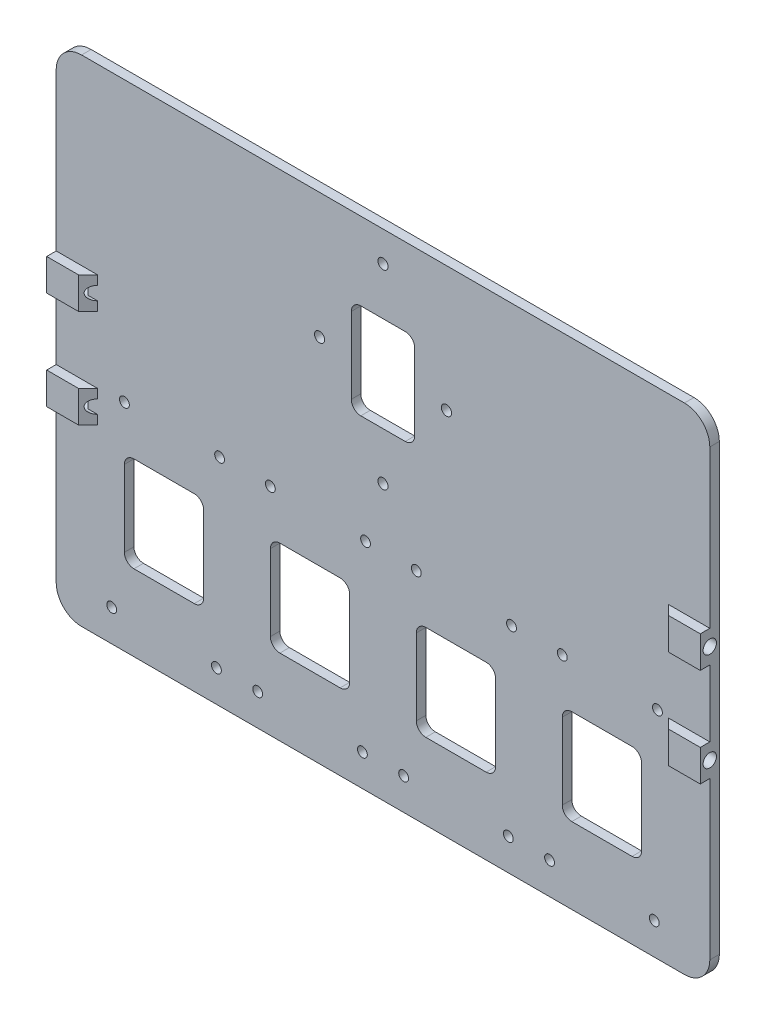
SolidWorks part; units mm, degrees
ref_plane "Front Plane" through (0, 0, 0) normal (1, 0, 0) x (0, 1, 0)
ref_plane "Top Plane" through (0, 0, 0) normal (0, 0, 1) x (0, 1, 0)
ref_plane "Right Plane" through (0, 0, 0) normal (0, 1, 0) x (-1, 0, 0)
sketch "Sketch1" plane through (0, 0, 0) normal (0, 0, 1) x (0, 1, 0)
  line L6 (0, 0) -> (31.4193, 0) construction
  line L7 (-70, -103) -> (70, -103)
  line L8 (-78, -95) -> (-78, 95)
  line L9 (-70, 103) -> (70, 103)
  line L10 (78, -95) -> (78, 95)
  line L11 (-78, -103) -> (78, 103) construction
  line L12 (-78, 103) -> (78, -103) construction
  line L13 (-68, -85.5) -> (-68, -52.5) construction
  line L15 (-10, -86.5) -> (-10, -56.5) construction
  line L23 (38.504, 27.5) -> (38.504, -27.5) construction
  line L25 (-78, 0) -> (-68, 0) construction
  line L30 (68, 0) -> (78, 0) construction
  line L34 (-73, -47.5) -> (-6, -47.5) construction
  line L35 (-73, -47.5) -> (-73, -90.5) construction
  line L40 (-73, -90.5) -> (-6, -90.5) construction
  line L41 (-6, -47.5) -> (-6, -90.5) construction
  line L42 (8.504, 20) -> (68.504, 20) construction
  line L43 (8.504, 20) -> (8.504, -20) construction
  line L44 (8.504, -20) -> (68.504, -20) construction
  line L45 (68.504, 20) -> (68.504, -20) construction
  line L46 (1.004, 27.5) -> (76.004, 27.5) construction
  line L47 (1.004, 27.5) -> (1.004, -27.5) construction
  line L48 (1.004, -27.5) -> (76.004, -27.5) construction
  line L49 (76.004, 27.5) -> (76.004, -27.5) construction
  arc A4 (70, -103) -> (78, -95) centre (70, -95) ccw
  arc A5 (-70, -103) -> (-78, -95) centre (-70, -95) cw
  arc A6 (-78, 95) -> (-70, 103) centre (-70, 95) cw
  arc A7 (70, 103) -> (78, 95) centre (70, 95) cw
  circle A8 centre (-68, -52.5) radius 1.55
  circle A9 centre (-68, -85.5) radius 1.55
  circle A10 centre (-10, -86.5) radius 1.55
  circle A11 centre (-10, -56.5) radius 1.55
  circle A24 centre (-68, -6.5) radius 1.55
  circle A25 centre (-68, -39.5) radius 1.55
  circle A26 centre (-10, -40.5) radius 1.55
  circle A27 centre (-10, -10.5) radius 1.55
  circle A28 centre (-68, 39.5) radius 1.55
  circle A29 centre (-68, 6.5) radius 1.55
  circle A30 centre (-10, 5.5) radius 1.55
  circle A31 centre (-10, 35.5) radius 1.55
  circle A32 centre (-68, 85.5) radius 1.55
  circle A33 centre (-68, 52.5) radius 1.55
  circle A34 centre (-10, 51.5) radius 1.55
  circle A35 centre (-10, 81.5) radius 1.55
  circle A40 centre (8.504, 0) radius 1.6
  circle A41 centre (38.504, 20) radius 1.6
  circle A42 centre (68.504, 0) radius 1.6
  circle A43 centre (38.504, -20) radius 1.6
  point P0 (0, 0)
  point P5 (0, 0)
  dimension "D6" = 8
  dimension "D8" = 3.1
  dimension "D19" = 3.2
  dimension "D1" = 156
  dimension "D3" = 206
  dimension "D7" = 33
  dimension "D10" = 30
  dimension "D5" = 10
  dimension "D4" = 43
  dimension "D11" = 67
  dimension "D12" = 5
  dimension "D13" = 5
  dimension "D9" = 4
  dimension "D15" = 4
  dimension "D16" = 13
  dimension "D17" = 40
  dimension "D18" = 60
  dimension "D21" = 55
  dimension "D22" = 75
  dimension "D20" = 1.996
  dimension "D14" = 4
extrude "Boss-Extrude1" add sketch "Sketch1" along normal blind 3
sketch "Sketch4" plane through (0, 0, 3) normal (0, 0, 1) x (1, 0, 0)
  line L0 (-69, -10) -> (-69, -68) construction
  line L1 (-78.5, -24) -> (-59.5, -24)
  line L2 (-81.5, -27) -> (-81.5, -51)
  line L3 (-78.5, -54) -> (-59.5, -54)
  line L4 (-56.5, -27) -> (-56.5, -51)
  line L5 (-81.5, -10) -> (-51.5, -10) construction
  line L6 (-85.5, -68) -> (-52.5, -68) construction
  line L7 (-81.5, -39) -> (-69, -39) construction
  line L8 (-35.5, -27) -> (-35.5, -51)
  line L9 (-32.5, -24) -> (-13.5, -24)
  line L10 (-32.5, -54) -> (-13.5, -54)
  line L11 (-10.5, -27) -> (-10.5, -51)
  line L12 (10.5, -27) -> (10.5, -51)
  line L13 (13.5, -24) -> (32.5, -24)
  line L14 (13.5, -54) -> (32.5, -54)
  line L15 (35.5, -27) -> (35.5, -51)
  line L16 (56.5, -27) -> (56.5, -51)
  line L17 (59.5, -24) -> (78.5, -24)
  line L18 (59.5, -54) -> (78.5, -54)
  line L19 (81.5, -27) -> (81.5, -51)
  line L20 (69, -8.2965) -> (69, -68) construction
  line L21 (52.5, -68) -> (85.5, -68) construction
  line L22 (-20, 38.504) -> (20, 38.504) construction
  line L23 (-7, 53.504) -> (7, 53.504)
  line L24 (-10, 50.504) -> (-10, 26.504)
  line L25 (-7, 23.504) -> (7, 23.504)
  line L26 (10, 50.504) -> (10, 26.504)
  line L27 (0, 68.504) -> (0, 8.504) construction
  arc A0 (78.5, -54) -> (81.5, -51) centre (78.5, -51) ccw
  arc A1 (78.5, -24) -> (81.5, -27) centre (78.5, -27) cw
  arc A2 (56.5, -27) -> (59.5, -24) centre (59.5, -27) cw
  arc A3 (56.5, -51) -> (59.5, -54) centre (59.5, -51) ccw
  arc A4 (32.5, -24) -> (35.5, -27) centre (32.5, -27) cw
  arc A5 (32.5, -54) -> (35.5, -51) centre (32.5, -51) ccw
  arc A6 (10.5, -51) -> (13.5, -54) centre (13.5, -51) ccw
  arc A7 (10.5, -27) -> (13.5, -24) centre (13.5, -27) cw
  arc A8 (-13.5, -54) -> (-10.5, -51) centre (-13.5, -51) ccw
  arc A9 (-13.5, -24) -> (-10.5, -27) centre (-13.5, -27) cw
  arc A10 (-35.5, -27) -> (-32.5, -24) centre (-32.5, -27) cw
  arc A11 (-35.5, -51) -> (-32.5, -54) centre (-32.5, -51) ccw
  arc A12 (-59.5, -54) -> (-56.5, -51) centre (-59.5, -51) ccw
  arc A13 (-81.5, -51) -> (-78.5, -54) centre (-78.5, -51) ccw
  arc A14 (-59.5, -24) -> (-56.5, -27) centre (-59.5, -27) cw
  arc A15 (-78.5, -24) -> (-81.5, -27) centre (-78.5, -27) ccw
  arc A16 (-10, 26.504) -> (-7, 23.504) centre (-7, 26.504) ccw
  arc A17 (7, 23.504) -> (10, 26.504) centre (7, 26.504) ccw
  arc A18 (7, 53.504) -> (10, 50.504) centre (7, 50.504) cw
  arc A19 (-7, 53.504) -> (-10, 50.504) centre (-7, 50.504) ccw
  point P5 (-58.5, -8.5)
  point P11 (-58.5, -8.5)
  point P67 (-56.5, -54)
  point P72 (-56.5, -24)
  point P75 (-81.5, -24)
  point P98 (10, 23.504)
  point P101 (10, 53.504)
  point P104 (-10, 53.504)
  dimension "D4" = 3
  dimension "D7" = 3
  dimension "D1" = 25
  dimension "D2" = 30
  dimension "D3" = 4
  dimension "D5" = 20
  dimension "D6" = 30
extrude "Cut-Extrude3" cut sketch "Sketch4" against normal up to next
sketch "Sketch3" plane through (103, 0, 0) normal (1, 0, 0) x (0, 1, 0)
  line L0 (0, 3) -> (0, 0) construction
  line L1 (-70, 3) -> (70, 3) construction
  line L2 (-70, 0) -> (70, 0) construction
  line L3 (-20.5, 3) -> (-10.5, 3) construction
  line L7 (-20.5, 6) -> (-10.5, 6)
  line L8 (-20.5, 6) -> (-20.5, 0)
  line L9 (-20.5, 0) -> (-10.5, 0)
  line L10 (-10.5, 6) -> (-10.5, 0)
  line L11 (10.5, 6) -> (20.5, 6)
  line L12 (10.5, 6) -> (10.5, 0)
  line L13 (10.5, 0) -> (20.5, 0)
  line L14 (20.5, 6) -> (20.5, 0)
  circle A1 centre (-15.5, 3) radius 2.1
  circle A2 centre (15.5, 3) radius 2.1
  dimension "D2" = 4.2
  dimension "D3" = 31
  dimension "D4" = 10
  dimension "D5" = 6
extrude "Boss-Extrude2" add sketch "Sketch3" against normal blind 10 contours L7 L10 L9 L8 | L11 L14 L13 L12
extrude "Boss-Extrude3" add sketch "Sketch3<4>" along normal blind 10 from surface contours L10 L9 L8 L7 | L12 L13 L14 L11 starting at face at (-103, 0, 1.5)
sketch "Sketch3<4>" plane through (103, 0, 0) normal (1, 0, 0) x (0, 1, 0) same geometry as "Sketch3"
extrude "Cut-Extrude4" cut sketch "Sketch3<6>" against normal blind 10 contours A1 | A2
sketch "Sketch3<6>" plane through (103, 0, 0) normal (1, 0, 0) x (0, 1, 0) same geometry as "Sketch3"
extrude "Cut-Extrude5" cut sketch "Sketch3<7>" along normal blind 10 from surface contours A2 | A1 starting at face at (-103, 0, 3.5)
sketch "Sketch3<7>" plane through (103, 0, 0) normal (1, 0, 0) x (0, 1, 0) same geometry as "Sketch3"
chamfer "Chamfer1" distance 3 angle 45 4 edges at (93, -19.05, 3) (93, 11.95, 3) (-93, -19.05, 3) (-93, 11.95, 3)
equation "\"MotorDriverLength\"= 60mm"
equation "\"MotorLength\"= 60"
equation "\"MotorDriverWidth\"=44"
equation "\"MotorWidth\"= 37"
equation "\"InnerWallThickness\"=3"
equation "\"BatteryWidth\"= 60"
equation "\"OuterWallThickness\" = 6"
equation "\"CompartmentHeight\"=37"
equation "\"CompartmentWidth\"= \"MotorDriverLength\""
equation "\"MotorDiameter\"=37"
equation "\"BatteryHeight\"=24.2019"
equation "\"MotorDriverHeight\"=28"
equation "\"CircuitHeight\"=30"
equation "\"FanThickness\"= 10"
equation "\"FanHeight\"=50"
equation "\"MotorShaftHole\"=12"
equation "\"BearingBore\"=4"
equation "\"MinShinWidth\"= 20"
equation "\"ShinThickness\"=10"
equation "\"PivotDistance\"=30"
equation "\"ThighLength\"= 200"
equation "\"KneeLength\" =20"
equation "\"HipBore\"=27"
equation "\"ThighThickness\"=20"
equation "\"MaxBending\"=135"
equation "\"MaxStretchingAngle\"= 140"
equation "\"ThighJointDistance\"=157.485"
equation "\"ShinLength\"=120"
equation "\"BearingDiameter\"= 10"
equation "\"CircuitLength\"=50"
equation "\"ChessisInnerWidth\"= \"OuterWallThickness\" * 2 + \"MotorDriverLength\" + \"MotorDiameter\" + \"InnerWallThickness\" * 3 + \"CircuitLength\""
equation "\"ChessisHeight\"= \"BatteryHeight\" + 10 + \"InnerWallThickness\" + \"MotorDiameter\" + 10 + \"OuterWallThickness\" * 2"
equation "\"ChassisWidth\"= \"MotorDriverWidth\"*4+30"
equation "\"D3@Sketch1\"=\"ChassisWidth\""
equation "\"D1@Sketch1\"=\"ChessisInnerWidth\"-\"OuterWallThickness\"*2"
